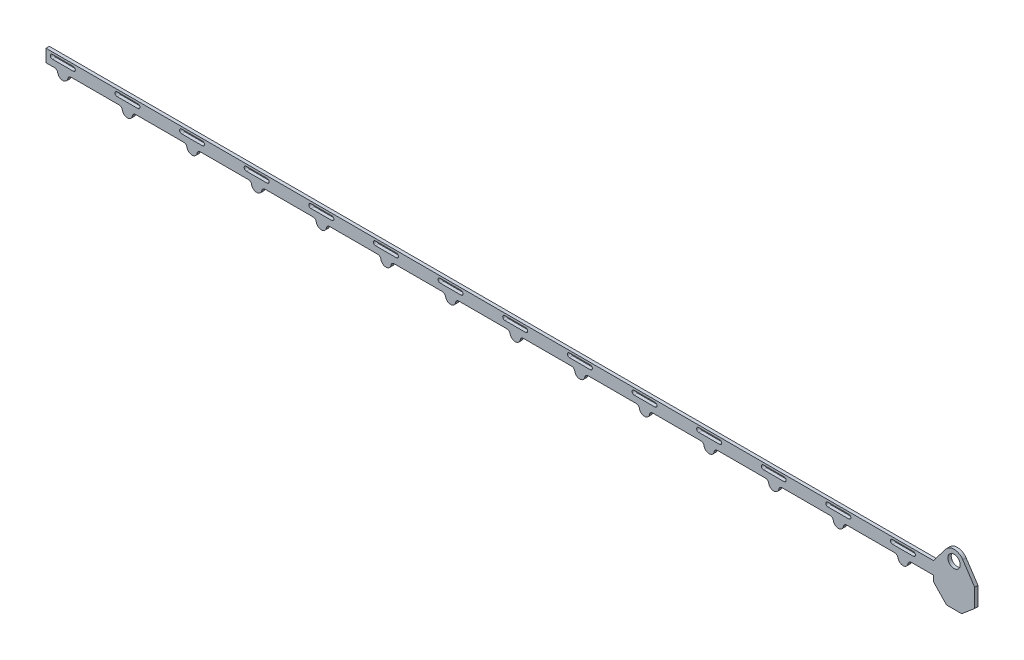
SolidWorks part; units mm, degrees
material "6061-T6 (SS)"
ref_plane "Front Plane" through (0, 0, 0) normal (0, 0, 1) x (1, 0, 0)
ref_plane "Top Plane" through (0, 0, 0) normal (0, 1, 0) x (1, 0, 0)
ref_plane "Right Plane" through (0, 0, 0) normal (1, 0, 0) x (0, 0, -1)
sketch "Sketch1" plane through (0, 0, 0) normal (0, 0, 1) x (1, 0, 0)
  line L0 (9.8044, 12.7762) -> (41.4274, 12.7762) construction
  line L1 (0, 0) -> (12.8989, 0)
  line L2 (0, 0) -> (0, 19.177)
  line L3 (0, 19.177) -> (1353.185, 19.177)
  line L4 (1416.05, 15.367) -> (1416.05, -12.7762)
  line L5 (9.8044, 15.9512) -> (41.4274, 15.9512)
  line L6 (9.8044, 9.6012) -> (41.4274, 9.6012)
  line L7 (108.3564, 12.7762) -> (139.9794, 12.7762) construction
  line L8 (108.3564, 15.9512) -> (139.9794, 15.9512)
  line L9 (108.3564, 9.6012) -> (139.9794, 9.6012)
  line L10 (206.9084, 12.7762) -> (238.5314, 12.7762) construction
  line L11 (206.9084, 15.9512) -> (238.5314, 15.9512)
  line L12 (206.9084, 9.6012) -> (238.5314, 9.6012)
  line L13 (305.4604, 12.7762) -> (337.0834, 12.7762) construction
  line L14 (305.4604, 15.9512) -> (337.0834, 15.9512)
  line L15 (305.4604, 9.6012) -> (337.0834, 9.6012)
  line L16 (404.0124, 12.7762) -> (435.6354, 12.7762) construction
  line L17 (404.0124, 15.9512) -> (435.6354, 15.9512)
  line L18 (404.0124, 9.6012) -> (435.6354, 9.6012)
  line L19 (502.5644, 12.7762) -> (534.1874, 12.7762) construction
  line L20 (502.5644, 15.9512) -> (534.1874, 15.9512)
  line L21 (502.5644, 9.6012) -> (534.1874, 9.6012)
  line L22 (601.1164, 12.7762) -> (632.7394, 12.7762) construction
  line L23 (601.1164, 15.9512) -> (632.7394, 15.9512)
  line L24 (601.1164, 9.6012) -> (632.7394, 9.6012)
  line L25 (699.6684, 12.7762) -> (731.2914, 12.7762) construction
  line L26 (699.6684, 15.9512) -> (731.2914, 15.9512)
  line L27 (699.6684, 9.6012) -> (731.2914, 9.6012)
  line L28 (798.2204, 12.7762) -> (829.8434, 12.7762) construction
  line L29 (798.2204, 15.9512) -> (829.8434, 15.9512)
  line L30 (798.2204, 9.6012) -> (829.8434, 9.6012)
  line L31 (896.7724, 12.7762) -> (928.3954, 12.7762) construction
  line L32 (896.7724, 15.9512) -> (928.3954, 15.9512)
  line L33 (896.7724, 9.6012) -> (928.3954, 9.6012)
  line L34 (995.3244, 12.7762) -> (1026.9474, 12.7762) construction
  line L35 (995.3244, 15.9512) -> (1026.9474, 15.9512)
  line L36 (995.3244, 9.6012) -> (1026.9474, 9.6012)
  line L37 (1093.8764, 12.7762) -> (1125.4994, 12.7762) construction
  line L38 (1093.8764, 15.9512) -> (1125.4994, 15.9512)
  line L39 (1093.8764, 9.6012) -> (1125.4994, 9.6012)
  line L40 (1192.4284, 12.7762) -> (1224.0514, 12.7762) construction
  line L41 (1192.4284, 15.9512) -> (1224.0514, 15.9512)
  line L42 (1192.4284, 9.6012) -> (1224.0514, 9.6012)
  line L43 (1290.9804, 12.7762) -> (1322.6034, 12.7762) construction
  line L44 (1290.9804, 15.9512) -> (1322.6034, 15.9512)
  line L45 (1290.9804, 9.6012) -> (1322.6034, 9.6012)
  line L46 (38.3329, 0) -> (111.4509, 0)
  line L47 (136.8849, 0) -> (210.0029, 0)
  line L48 (235.4369, 0) -> (308.5549, 0)
  line L49 (333.9889, 0) -> (407.1069, 0)
  line L50 (432.5409, 0) -> (505.6589, 0)
  line L51 (531.0929, 0) -> (604.2109, 0)
  line L52 (629.6449, 0) -> (702.7629, 0)
  line L53 (728.1969, 0) -> (801.3149, 0)
  line L54 (826.7489, 0) -> (899.8669, 0)
  line L55 (925.3009, 0) -> (998.4189, 0)
  line L56 (1023.8529, 0) -> (1096.9709, 0)
  line L57 (1122.4049, 0) -> (1195.5229, 0)
  line L58 (1220.9569, 0) -> (1294.0749, 0)
  line L59 (1319.5089, 0) -> (1353.185, 0)
  line L60 (1416.05, 15.367) -> (1397.9567, 42.6719)
  line L62 (1371.9264, 43.5796) -> (1353.185, 19.177)
  line L63 (1353.185, 0) -> (1353.185, -8.6614)
  line L64 (1353.185, -8.6614) -> (1373.0986, -29.4894)
  line L65 (1373.0986, -29.4894) -> (1396.1364, -29.4894)
  line L66 (1396.1364, -29.4894) -> (1416.05, -12.7762)
  line L67 (1353.185, 19.177) -> (1416.05, 19.177) construction
  arc A0 (9.8044, 15.9512) -> (9.8044, 9.6012) centre (9.8044, 12.7762) ccw
  arc A1 (41.4274, 9.6012) -> (41.4274, 15.9512) centre (41.4274, 12.7762) ccw
  arc A2 (108.3564, 15.9512) -> (108.3564, 9.6012) centre (108.3564, 12.7762) ccw
  arc A3 (139.9794, 9.6012) -> (139.9794, 15.9512) centre (139.9794, 12.7762) ccw
  arc A4 (206.9084, 15.9512) -> (206.9084, 9.6012) centre (206.9084, 12.7762) ccw
  arc A5 (238.5314, 9.6012) -> (238.5314, 15.9512) centre (238.5314, 12.7762) ccw
  arc A6 (305.4604, 15.9512) -> (305.4604, 9.6012) centre (305.4604, 12.7762) ccw
  arc A7 (337.0834, 9.6012) -> (337.0834, 15.9512) centre (337.0834, 12.7762) ccw
  arc A8 (404.0124, 15.9512) -> (404.0124, 9.6012) centre (404.0124, 12.7762) ccw
  arc A9 (435.6354, 9.6012) -> (435.6354, 15.9512) centre (435.6354, 12.7762) ccw
  arc A10 (502.5644, 15.9512) -> (502.5644, 9.6012) centre (502.5644, 12.7762) ccw
  arc A11 (534.1874, 9.6012) -> (534.1874, 15.9512) centre (534.1874, 12.7762) ccw
  arc A12 (601.1164, 15.9512) -> (601.1164, 9.6012) centre (601.1164, 12.7762) ccw
  arc A13 (632.7394, 9.6012) -> (632.7394, 15.9512) centre (632.7394, 12.7762) ccw
  arc A14 (699.6684, 15.9512) -> (699.6684, 9.6012) centre (699.6684, 12.7762) ccw
  arc A15 (731.2914, 9.6012) -> (731.2914, 15.9512) centre (731.2914, 12.7762) ccw
  arc A16 (798.2204, 15.9512) -> (798.2204, 9.6012) centre (798.2204, 12.7762) ccw
  arc A17 (829.8434, 9.6012) -> (829.8434, 15.9512) centre (829.8434, 12.7762) ccw
  arc A18 (896.7724, 15.9512) -> (896.7724, 9.6012) centre (896.7724, 12.7762) ccw
  arc A19 (928.3954, 9.6012) -> (928.3954, 15.9512) centre (928.3954, 12.7762) ccw
  arc A20 (995.3244, 15.9512) -> (995.3244, 9.6012) centre (995.3244, 12.7762) ccw
  arc A21 (1026.9474, 9.6012) -> (1026.9474, 15.9512) centre (1026.9474, 12.7762) ccw
  arc A22 (1093.8764, 15.9512) -> (1093.8764, 9.6012) centre (1093.8764, 12.7762) ccw
  arc A23 (1125.4994, 9.6012) -> (1125.4994, 15.9512) centre (1125.4994, 12.7762) ccw
  arc A24 (1192.4284, 15.9512) -> (1192.4284, 9.6012) centre (1192.4284, 12.7762) ccw
  arc A25 (1224.0514, 9.6012) -> (1224.0514, 15.9512) centre (1224.0514, 12.7762) ccw
  arc A26 (1290.9804, 15.9512) -> (1290.9804, 9.6012) centre (1290.9804, 12.7762) ccw
  arc A27 (1322.6034, 9.6012) -> (1322.6034, 15.9512) centre (1322.6034, 12.7762) ccw
  arc A28 (17.9056, -4.22) -> (33.3262, -4.22) centre (25.6159, -2.8956) ccw
  arc A29 (116.4576, -4.22) -> (111.4509, 0) centre (111.4509, -5.08) ccw
  arc A30 (116.4576, -4.22) -> (131.8782, -4.22) centre (124.1679, -2.8956) ccw
  arc A31 (136.8849, 0) -> (131.8782, -4.22) centre (136.8849, -5.08) ccw
  arc A32 (215.0096, -4.22) -> (210.0029, 0) centre (210.0029, -5.08) ccw
  arc A33 (215.0096, -4.22) -> (230.4302, -4.22) centre (222.7199, -2.8956) ccw
  arc A34 (235.4369, 0) -> (230.4302, -4.22) centre (235.4369, -5.08) ccw
  arc A35 (313.5616, -4.22) -> (308.5549, 0) centre (308.5549, -5.08) ccw
  arc A36 (313.5616, -4.22) -> (328.9822, -4.22) centre (321.2719, -2.8956) ccw
  arc A37 (333.9889, 0) -> (328.9822, -4.22) centre (333.9889, -5.08) ccw
  arc A38 (412.1136, -4.22) -> (407.1069, 0) centre (407.1069, -5.08) ccw
  arc A39 (412.1136, -4.22) -> (427.5342, -4.22) centre (419.8239, -2.8956) ccw
  arc A40 (432.5409, 0) -> (427.5342, -4.22) centre (432.5409, -5.08) ccw
  arc A41 (510.6656, -4.22) -> (505.6589, 0) centre (505.6589, -5.08) ccw
  arc A42 (17.9056, -4.22) -> (12.8989, 0) centre (12.8989, -5.08) ccw
  arc A43 (38.3329, 0) -> (33.3262, -4.22) centre (38.3329, -5.08) ccw
  arc A44 (510.6656, -4.22) -> (526.0862, -4.22) centre (518.3759, -2.8956) ccw
  arc A45 (531.0929, 0) -> (526.0862, -4.22) centre (531.0929, -5.08) ccw
  arc A46 (609.2176, -4.22) -> (604.2109, 0) centre (604.2109, -5.08) ccw
  arc A47 (609.2176, -4.22) -> (624.6382, -4.22) centre (616.9279, -2.8956) ccw
  arc A48 (629.6449, 0) -> (624.6382, -4.22) centre (629.6449, -5.08) ccw
  arc A49 (707.7696, -4.22) -> (702.7629, 0) centre (702.7629, -5.08) ccw
  arc A50 (707.7696, -4.22) -> (723.1902, -4.22) centre (715.4799, -2.8956) ccw
  arc A51 (728.1969, 0) -> (723.1902, -4.22) centre (728.1969, -5.08) ccw
  arc A52 (806.3216, -4.22) -> (801.3149, 0) centre (801.3149, -5.08) ccw
  arc A53 (806.3216, -4.22) -> (821.7422, -4.22) centre (814.0319, -2.8956) ccw
  arc A54 (826.7489, 0) -> (821.7422, -4.22) centre (826.7489, -5.08) ccw
  arc A55 (904.8736, -4.22) -> (899.8669, 0) centre (899.8669, -5.08) ccw
  arc A56 (904.8736, -4.22) -> (920.2942, -4.22) centre (912.5839, -2.8956) ccw
  arc A57 (925.3009, 0) -> (920.2942, -4.22) centre (925.3009, -5.08) ccw
  arc A58 (1003.4256, -4.22) -> (998.4189, 0) centre (998.4189, -5.08) ccw
  arc A59 (1003.4256, -4.22) -> (1018.8462, -4.22) centre (1011.1359, -2.8956) ccw
  arc A60 (1023.8529, 0) -> (1018.8462, -4.22) centre (1023.8529, -5.08) ccw
  arc A61 (1101.9776, -4.22) -> (1096.9709, 0) centre (1096.9709, -5.08) ccw
  arc A62 (1101.9776, -4.22) -> (1117.3982, -4.22) centre (1109.6879, -2.8956) ccw
  arc A63 (1122.4049, 0) -> (1117.3982, -4.22) centre (1122.4049, -5.08) ccw
  arc A64 (1200.5296, -4.22) -> (1195.5229, 0) centre (1195.5229, -5.08) ccw
  arc A65 (1200.5296, -4.22) -> (1215.9502, -4.22) centre (1208.2399, -2.8956) ccw
  arc A66 (1220.9569, 0) -> (1215.9502, -4.22) centre (1220.9569, -5.08) ccw
  arc A67 (1299.0816, -4.22) -> (1294.0749, 0) centre (1294.0749, -5.08) ccw
  arc A68 (1299.0816, -4.22) -> (1314.5022, -4.22) centre (1306.7919, -2.8956) ccw
  arc A69 (1319.5089, 0) -> (1314.5022, -4.22) centre (1319.5089, -5.08) ccw
  arc A70 (1397.9567, 42.6719) -> (1371.9264, 43.5796) centre (1384.6175, 33.8328) ccw
  circle A71 centre (1384.6175, 33.8328) radius 9.398
  point P7 (25.6159, 12.7762)
  point P12 (44.6024, 12.7762)
  point P13 (6.6294, 12.7762)
  point P18 (124.1679, 12.7762)
  point P25 (222.7199, 12.7762)
  point P32 (321.2719, 12.7762)
  point P39 (419.8239, 12.7762)
  point P46 (518.3759, 12.7762)
  point P53 (616.9279, 12.7762)
  point P60 (715.4799, 12.7762)
  point P67 (814.0319, 12.7762)
  point P74 (912.5839, 12.7762)
  point P81 (1011.1359, 12.7762)
  point P88 (1109.6879, 12.7762)
  point P95 (1208.2399, 12.7762)
  point P102 (1306.7919, 12.7762)
  point P213 (1384.6175, -29.4894)
  point P214 (1384.6175, 19.177)
  dimension "D6" = 15.6464
  dimension "D9" = 10.16
  dimension "D10" = 10.16
  dimension "D14" = 32.004
  dimension "D20" = 18.796
  dimension "D1" = 1416.05
  dimension "D2" = 19.177
  dimension "D3" = 37.973
  dimension "D4" = 6.35
  dimension "D5" = 14
  dimension "D7" = 22.0726
  dimension "D8" = 14
  dimension "D11" = 29.4894
  dimension "D12" = 28.1432
  dimension "D13" = 23.0378
  dimension "D15" = 63.3222
  dimension "D16" = 3.81
  dimension "D17" = 8.6614
  dimension "D18" = 62.865
  dimension "D19" = 98.552
  dimension "D31" = 3.2258
  dimension "D32" = 6.6294
extrude "Boss-Extrude1" add sketch "Sketch1" along normal blind 5.08 contours L3 L62 A70 L60 L4 L66 L65 L64 L63 L59 A69 A68 A67 L58 A66 A65 A64 L57 A63 A62 A61 L56 A60 A59 A58 L55 A57 A56 A55 L54 A54 A53 A52 L53 A51 A50 A49 L52 A48 A47 A46 L51 A45 A44 A41 L50 A40 A39 A38 L49 A37 A36 A35 L48 A34 A33 A32 L47 A31 A30 A29 L46 A43 A28 A42 L1 L2
sketch "Sketch2" plane through (0, 0, 5.08) normal (0, 0, 1) x (1, 0, 0)
  line L0 (9.7409, 12.7762) -> (41.4909, 12.7762) construction
  line L1 (9.7409, 15.9512) -> (41.4909, 15.9512)
  line L2 (9.7409, 9.6012) -> (41.4909, 9.6012)
  line L3 (108.2929, 12.7762) -> (140.0429, 12.7762) construction
  line L4 (108.2929, 15.9512) -> (140.0429, 15.9512)
  line L5 (108.2929, 9.6012) -> (140.0429, 9.6012)
  line L6 (206.8449, 12.7762) -> (238.5949, 12.7762) construction
  line L7 (206.8449, 15.9512) -> (238.5949, 15.9512)
  line L8 (206.8449, 9.6012) -> (238.5949, 9.6012)
  line L9 (305.3969, 12.7762) -> (337.1469, 12.7762) construction
  line L10 (305.3969, 15.9512) -> (337.1469, 15.9512)
  line L11 (305.3969, 9.6012) -> (337.1469, 9.6012)
  line L12 (403.9489, 12.7762) -> (435.6989, 12.7762) construction
  line L13 (403.9489, 15.9512) -> (435.6989, 15.9512)
  line L14 (403.9489, 9.6012) -> (435.6989, 9.6012)
  line L15 (502.5009, 12.7762) -> (534.2509, 12.7762) construction
  line L16 (502.5009, 15.9512) -> (534.2509, 15.9512)
  line L17 (502.5009, 9.6012) -> (534.2509, 9.6012)
  line L18 (601.0529, 12.7762) -> (632.8029, 12.7762) construction
  line L19 (601.0529, 15.9512) -> (632.8029, 15.9512)
  line L20 (601.0529, 9.6012) -> (632.8029, 9.6012)
  line L21 (699.6049, 12.7762) -> (731.3549, 12.7762) construction
  line L22 (699.6049, 15.9512) -> (731.3549, 15.9512)
  line L23 (699.6049, 9.6012) -> (731.3549, 9.6012)
  line L24 (798.1569, 12.7762) -> (829.9069, 12.7762) construction
  line L25 (798.1569, 15.9512) -> (829.9069, 15.9512)
  line L26 (798.1569, 9.6012) -> (829.9069, 9.6012)
  line L27 (896.7089, 12.7762) -> (928.4589, 12.7762) construction
  line L28 (896.7089, 15.9512) -> (928.4589, 15.9512)
  line L29 (896.7089, 9.6012) -> (928.4589, 9.6012)
  line L30 (995.2609, 12.7762) -> (1027.0109, 12.7762) construction
  line L31 (995.2609, 15.9512) -> (1027.0109, 15.9512)
  line L32 (995.2609, 9.6012) -> (1027.0109, 9.6012)
  line L33 (1093.8129, 12.7762) -> (1125.5629, 12.7762) construction
  line L34 (1093.8129, 15.9512) -> (1125.5629, 15.9512)
  line L35 (1093.8129, 9.6012) -> (1125.5629, 9.6012)
  line L36 (1192.3649, 12.7762) -> (1224.1149, 12.7762) construction
  line L37 (1192.3649, 15.9512) -> (1224.1149, 15.9512)
  line L38 (1192.3649, 9.6012) -> (1224.1149, 9.6012)
  line L39 (1290.9169, 12.7762) -> (1322.6669, 12.7762) construction
  line L40 (1290.9169, 15.9512) -> (1322.6669, 15.9512)
  line L41 (1290.9169, 9.6012) -> (1322.6669, 9.6012)
  arc A0 (9.7409, 15.9512) -> (9.7409, 9.6012) centre (9.7409, 12.7762) ccw
  arc A1 (41.4909, 9.6012) -> (41.4909, 15.9512) centre (41.4909, 12.7762) ccw
  arc A2 (108.2929, 15.9512) -> (108.2929, 9.6012) centre (108.2929, 12.7762) ccw
  arc A3 (140.0429, 9.6012) -> (140.0429, 15.9512) centre (140.0429, 12.7762) ccw
  arc A4 (206.8449, 15.9512) -> (206.8449, 9.6012) centre (206.8449, 12.7762) ccw
  arc A5 (238.5949, 9.6012) -> (238.5949, 15.9512) centre (238.5949, 12.7762) ccw
  arc A6 (305.3969, 15.9512) -> (305.3969, 9.6012) centre (305.3969, 12.7762) ccw
  arc A7 (337.1469, 9.6012) -> (337.1469, 15.9512) centre (337.1469, 12.7762) ccw
  arc A8 (403.9489, 15.9512) -> (403.9489, 9.6012) centre (403.9489, 12.7762) ccw
  arc A9 (435.6989, 9.6012) -> (435.6989, 15.9512) centre (435.6989, 12.7762) ccw
  arc A10 (502.5009, 15.9512) -> (502.5009, 9.6012) centre (502.5009, 12.7762) ccw
  arc A11 (534.2509, 9.6012) -> (534.2509, 15.9512) centre (534.2509, 12.7762) ccw
  arc A12 (601.0529, 15.9512) -> (601.0529, 9.6012) centre (601.0529, 12.7762) ccw
  arc A13 (632.8029, 9.6012) -> (632.8029, 15.9512) centre (632.8029, 12.7762) ccw
  arc A14 (699.6049, 15.9512) -> (699.6049, 9.6012) centre (699.6049, 12.7762) ccw
  arc A15 (731.3549, 9.6012) -> (731.3549, 15.9512) centre (731.3549, 12.7762) ccw
  arc A16 (798.1569, 15.9512) -> (798.1569, 9.6012) centre (798.1569, 12.7762) ccw
  arc A17 (829.9069, 9.6012) -> (829.9069, 15.9512) centre (829.9069, 12.7762) ccw
  arc A18 (896.7089, 15.9512) -> (896.7089, 9.6012) centre (896.7089, 12.7762) ccw
  arc A19 (928.4589, 9.6012) -> (928.4589, 15.9512) centre (928.4589, 12.7762) ccw
  arc A20 (995.2609, 15.9512) -> (995.2609, 9.6012) centre (995.2609, 12.7762) ccw
  arc A21 (1027.0109, 9.6012) -> (1027.0109, 15.9512) centre (1027.0109, 12.7762) ccw
  arc A22 (1093.8129, 15.9512) -> (1093.8129, 9.6012) centre (1093.8129, 12.7762) ccw
  arc A23 (1125.5629, 9.6012) -> (1125.5629, 15.9512) centre (1125.5629, 12.7762) ccw
  arc A24 (1192.3649, 15.9512) -> (1192.3649, 9.6012) centre (1192.3649, 12.7762) ccw
  arc A25 (1224.1149, 9.6012) -> (1224.1149, 15.9512) centre (1224.1149, 12.7762) ccw
  arc A26 (1290.9169, 15.9512) -> (1290.9169, 9.6012) centre (1290.9169, 12.7762) ccw
  arc A27 (1322.6669, 9.6012) -> (1322.6669, 15.9512) centre (1322.6669, 12.7762) ccw
  point P2 (25.6159, 12.7762)
  point P7 (6.5659, 12.7762)
  point P8 (44.6659, 12.7762)
  point P12 (124.1679, 12.7762)
  point P19 (222.7199, 12.7762)
  point P26 (321.2719, 12.7762)
  point P33 (419.8239, 12.7762)
  point P40 (518.3759, 12.7762)
  point P47 (616.9279, 12.7762)
  point P54 (715.4799, 12.7762)
  point P61 (814.0319, 12.7762)
  point P68 (912.5839, 12.7762)
  point P75 (1011.1359, 12.7762)
  point P82 (1109.6879, 12.7762)
  point P89 (1208.2399, 12.7762)
  point P98 (1306.7919, 12.7762)
  dimension "D1" = 38.1
  dimension "D2" = 6.35
  dimension "D3" = 14
extrude "Cut-Extrude4" cut sketch "Sketch2" against normal through all
extrude "Cut-Extrude7" cut sketch "Sketch1<4>" against normal through all and the other way through all contours A71
sketch "Sketch1<4>" plane through (0, 0, 0) normal (0, 0, 1) x (1, 0, 0) same geometry as "Sketch1"
